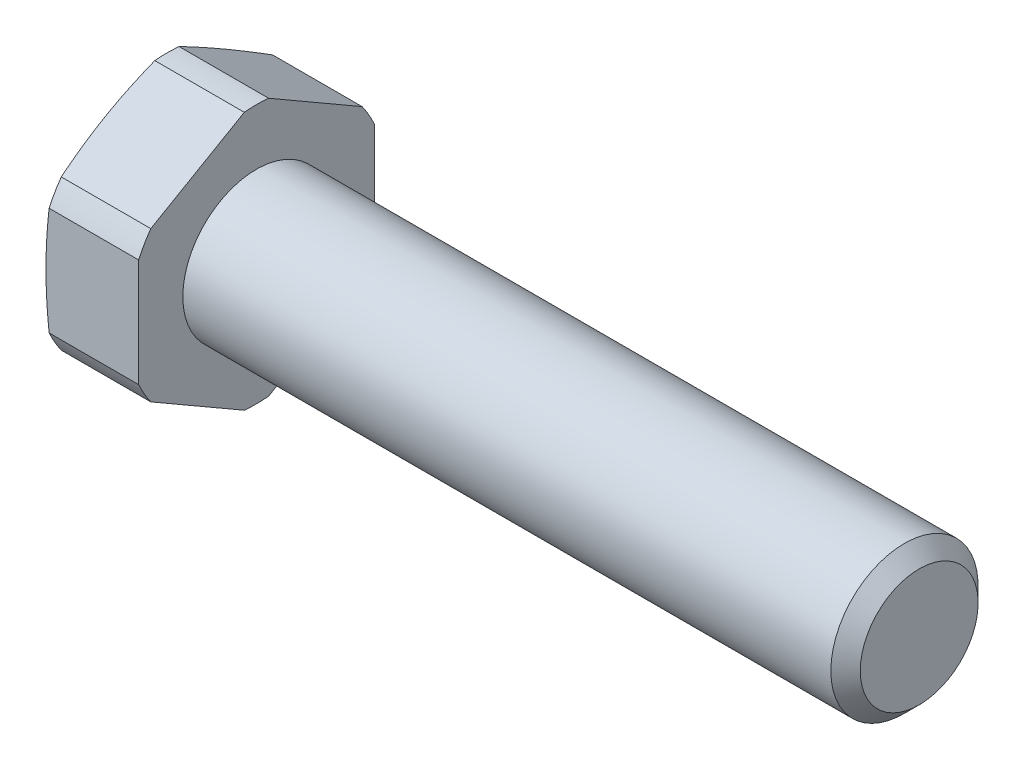
SolidWorks part; units mm, degrees
material "AISI 1020"
ref_plane "Спереди" through (0, 0, 0) normal (0, 0, 1) x (1, 0, 0)
ref_plane "Сверху" through (0, 0, 0) normal (0, 1, 0) x (1, 0, 0)
ref_plane "Справа" through (0, 0, 0) normal (1, 0, 0) x (0, 0, -1)
sketch "Эскиз1" plane through (0, 0, 0) normal (0, 0, 1) x (1, 0, 0)
  line L0 (-1000, 0) -> (49000, 0) construction
  line L1 (-6.4, 0) -> (-6.4, 7.6)
  line L2 (-6.4, 7.6) -> (-6.0785, 8.8)
  line L3 (-6.0785, 8.8) -> (0, 8.8)
  line L4 (0, 8.8) -> (0, 5)
  line L5 (0, 5) -> (44, 5)
  line L6 (45, 4) -> (45, 0)
  line L7 (45, 5) -> (45.75, 6.299) construction
  line L8 (45.75, 6.299) -> (46.5, 5) construction
  line L9 (46.5, 5) -> (45, 5) construction
  line L10 (45.75, 6.299) -> (45.75, 5) construction
  line L11 (45.75, 6.299) -> (19.75, 6.299) construction
  line L12 (44, 5) -> (45, 4)
  line L13 (45, 5) -> (44.5, 4.5) construction
  line L14 (-6.4, 7.6) -> (-22.4, 7.6) construction
  line L15 (-6.4, 0) -> (45, 0)
  dimension "D1" = 1
  dimension "D2" = 15
revolve "Повернуть1" add sketch "Эскиз1" angle 360 about L0
cosmetic thread "Условное изображение резьбы1" parameters "D1"=20, "D2"=7.4019
sketch "Эскиз2" plane through (-6.4, 0, 0) normal (-1, 0, 0) x (0, 0, 1)
  line L1 (0, 9.2376) -> (-8, 4.6188)
  line L2 (-8, 4.6188) -> (-8, -4.6188)
  line L3 (-8, -4.6188) -> (0, -9.2376)
  line L4 (0, -9.2376) -> (8, -4.6188)
  line L5 (8, -4.6188) -> (8, 4.6188)
  line L6 (8, 4.6188) -> (0, 9.2376)
  circle A0 centre (0, 0) radius 8 construction
  dimension "D1" = 16
extrude "Вырез-Вытянуть1" cut sketch "Эскиз2" against normal up to surface (51.4 mm away) flip side to cut up to face at (45, 0, 4)
equation "\"D1@Эскиз1\"=\"_d_@Эскиз1\"/10"
equation "\"D@Эскиз1\"=\"S_@Эскиз1\"*0.95"
equation "\"D1@Эскиз2\"=\"S_@Эскиз1\""
equation "\"D1@Условное изображение резьбы1\"=\"b_@Эскиз1\""
equation "\"D2@Условное изображение резьбы1\"=\"_d_@Эскиз1\"-\"dr@Эскиз1\"*2"
